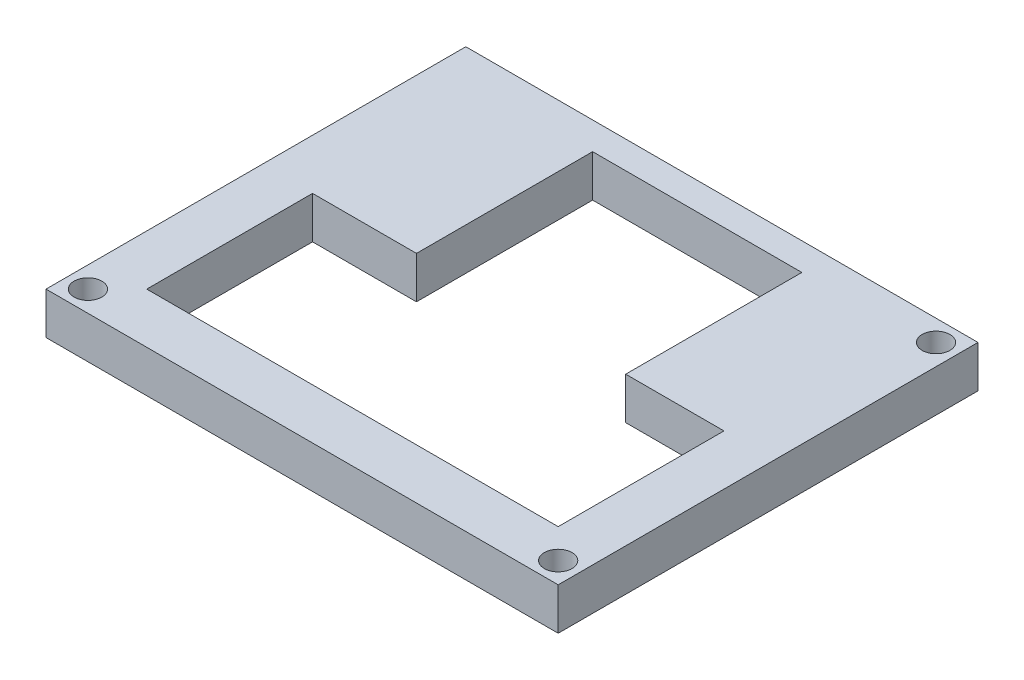
SolidWorks part; units mm, degrees
ref_plane "Front Plane" through (0, 0, 0) normal (0, 0, 1) x (1, 0, 0)
ref_plane "Top Plane" through (0, 0, 0) normal (0, 1, 0) x (1, 0, 0)
ref_plane "Right Plane" through (0, 0, 0) normal (1, 0, 0) x (0, 0, -1)
sketch "Sketch1" plane through (0, 0, 0) normal (0, 1, 0) x (1, 0, 0)
  line L1 (0, 0) -> (77.47, 0)
  line L2 (0, 0) -> (0, 63.5)
  line L3 (0, 63.5) -> (77.47, 63.5)
  line L4 (77.47, 0) -> (77.47, 63.5)
  line L5 (23.3376, 59.3441) -> (54.9824, 59.3441)
  line L6 (23.3376, 59.3441) -> (23.3376, 32.6975)
  line L7 (23.3376, 32.6975) -> (54.9824, 32.6975)
  line L8 (54.9824, 59.3441) -> (54.9824, 32.6975)
  line L9 (7.62, 32.6975) -> (69.85, 32.6975)
  line L10 (7.62, 32.6975) -> (7.62, 7.62)
  line L11 (7.62, 7.62) -> (69.85, 7.62)
  line L12 (69.85, 32.6975) -> (69.85, 7.62)
  dimension "D1" = 77.47
  dimension "D2" = 63.5
  dimension "D3" = 7.62
  dimension "D4" = 7.62
  dimension "D5" = 7.62
extrude "Boss-Extrude1" add sketch "Sketch1" along normal blind 6.35 contours L1 L4 L3 L2 L9 L12 L11 L10 L6 L5 L8 region at (1.0017, 0, -31.75)
sketch "Sketch2" plane through (0, 6.35, 0) normal (0, 1, 0) x (1, 0, 0)
  line L0 (0, 63.5) -> (77.47, 63.5) construction
  line L1 (77.47, 0) -> (77.47, 63.5) construction
  line L2 (0, 0) -> (77.47, 0) construction
  line L3 (0, 0) -> (0, 63.5) construction
  circle A0 centre (3.175, 3.175) radius 2.1
  circle A1 centre (74.295, 3.175) radius 2.1
  circle A2 centre (74.295, 60.325) radius 2.1
  point P6 (0, 0)
  point P7 (4.1209, 4.0676)
  point P8 (0, 0)
  point P9 (73.3491, 59.609)
  point P10 (4.4741, 4.5091)
  point P11 (72.9076, 4.9506)
  point P12 (4.1209, 4.5091)
  point P13 (0, 0)
  point P14 (73.5257, 59.4324)
  point P21 (4.4741, 3.175)
  dimension "D1" = 4.2
  dimension "D2" = 3.175
  dimension "D3" = 3.175
  dimension "D4" = 3.175
  dimension "D5" = 3.175
extrude "Cut-Extrude1" cut sketch "Sketch2" against normal blind 6.35
